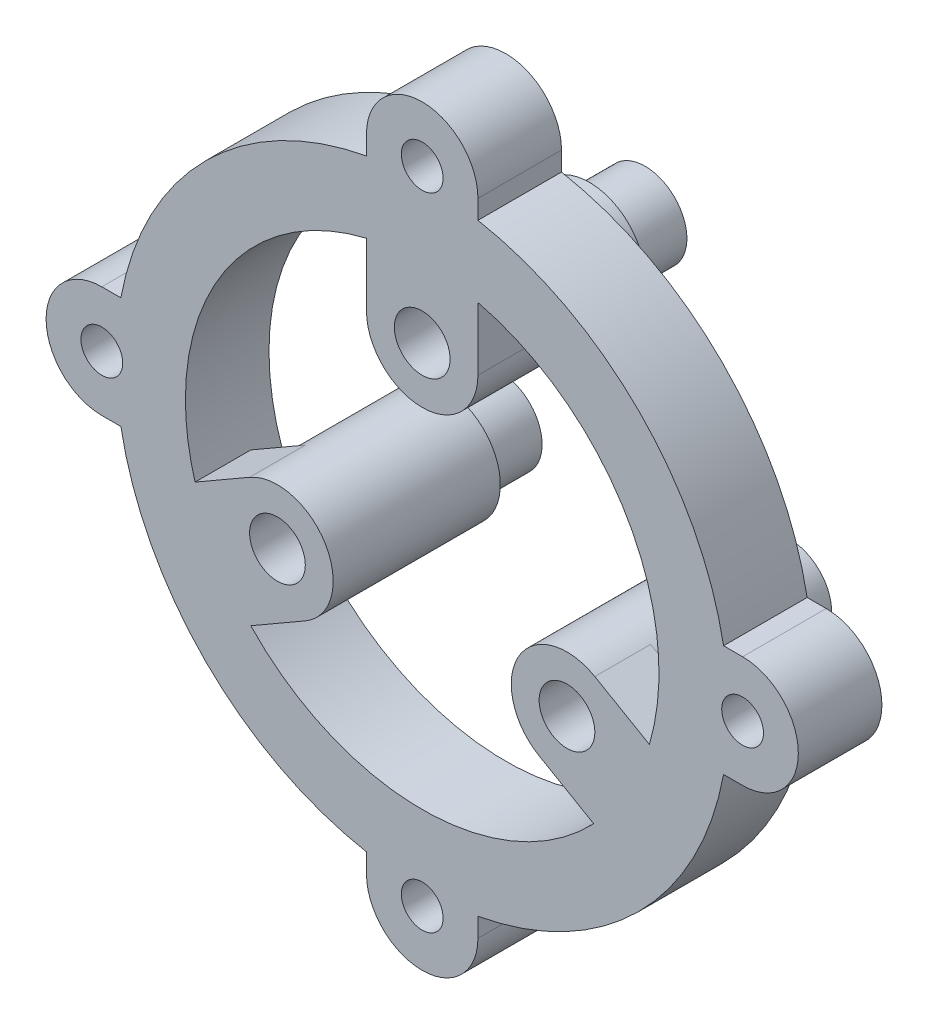
SolidWorks part; units mm, degrees
ref_plane "前视基准面" through (0, 0, 0) normal (0, 0, 1) x (1, 0, 0)
ref_plane "上视基准面" through (0, 0, 0) normal (0, 1, 0) x (1, 0, 0)
ref_plane "右视基准面" through (0, 0, 0) normal (1, 0, 0) x (0, 0, -1)
other "Configuration Table"
sketch "草图1" plane through (0, 0, 0) normal (0, 0, 1) x (1, 0, 0)
  line L0 (9.4853, -3.1669) -> (4, 0)
  line L5 (-2, 9.798) -> (-2, 3.4641)
  line L7 (2, 9.798) -> (2, 3.4641)
  line L8 (7.4853, -6.631) -> (2, -3.4641)
  line L9 (-7.4853, -6.631) -> (-2, -3.4641)
  line L10 (-9.4853, -3.1669) -> (-4, 0)
  circle A1 centre (0, 6) radius 1
  circle A2 centre (5.1962, -3) radius 1
  circle A3 centre (-5.1962, -3) radius 1
  arc A4 (-2, 3.4641) -> (-4, 0) centre (0, 0) ccw
  circle A6 centre (0, 11.5) radius 0.75
  circle A7 centre (11.5, 0) radius 0.75
  circle A8 centre (0, -11.5) radius 0.75
  circle A9 centre (-11.5, 0) radius 0.75
  arc A10 (-2, 9.798) -> (-9.4853, -3.1669) centre (0, 0) ccw
  circle A11 centre (0, 0) radius 13
  arc A13 (-2, -3.4641) -> (2, -3.4641) centre (0, 0) ccw
  arc A14 (-7.4853, -6.631) -> (7.4853, -6.631) centre (0, 0) ccw
  arc A15 (4, 0) -> (2, 3.4641) centre (0, 0) ccw
  arc A16 (9.4853, -3.1669) -> (2, 9.798) centre (0, 0) ccw
  point P12 (0, 0)
  point P22 (0, 0)
  point P35 (0, 0)
  dimension "D1" = 3
  dimension "D2" = 4
  dimension "D3" = 3
extrude "凸台-拉伸1" add sketch "草图1" along normal blind 3
sketch "草图2" plane through (0, 0, 0) normal (0, 0, -1) x (-1, 0, 0)
  circle A0 centre (0, 6) radius 2
  circle A1 centre (0, 6) radius 3
  circle A2 centre (5.1962, -3) radius 3
  circle A3 centre (5.1962, -3) radius 2
  circle A4 centre (-5.1962, -3) radius 3
  circle A5 centre (-5.1962, -3) radius 2
  arc A6 (4, 0) -> (2, 3.4641) centre (0, 0) ccw construction
  circle A7 centre (0, 11.5) radius 0.75
  circle A8 centre (0, 11.5) radius 2
  circle A9 centre (11.5, 0) radius 0.75
  circle A10 centre (11.5, 0) radius 2
  circle A11 centre (0, -11.5) radius 0.75
  circle A12 centre (0, -11.5) radius 2
  circle A13 centre (-11.5, 0) radius 0.75
  circle A14 centre (-11.5, 0) radius 2
  point P13 (0, 0)
  point P30 (0, 0)
  dimension "D1" = 3
  dimension "D2" = 4
extrude "凸台-拉伸2" add sketch "草图2" along normal blind 2 and the other way blind 3
sketch "草图3" plane through (0, 0, 0) normal (0, 0, -1) x (-1, 0, 0)
  line L2 (-2, 11.5) -> (-2, 10.8167)
  line L4 (2, 11.5) -> (2, 10.8167)
  line L5 (11.5, 2) -> (10.8167, 2)
  line L6 (11.5, -2) -> (10.8167, -2)
  line L7 (2, -11.5) -> (2, -10.8167)
  line L8 (-2, -11.5) -> (-2, -10.8167)
  line L9 (-11.5, -2) -> (-10.8167, -2)
  line L10 (-11.5, 2) -> (-10.8167, 2)
  arc A0 (2, 11.5) -> (-2, 11.5) centre (0, 11.5) ccw
  arc A2 (-2, 10.8167) -> (-10.8167, 2) centre (0, 0) ccw
  arc A3 (11.5, -2) -> (11.5, 2) centre (11.5, 0) ccw
  arc A4 (-2, -11.5) -> (2, -11.5) centre (0, -11.5) ccw
  arc A5 (-11.5, 2) -> (-11.5, -2) centre (-11.5, 0) ccw
  arc A6 (-10.8167, -2) -> (-2, -10.8167) centre (0, 0) ccw
  arc A7 (10.8167, 2) -> (2, 10.8167) centre (0, 0) ccw
  arc A8 (2, -10.8167) -> (10.8167, -2) centre (0, 0) ccw
  circle A9 centre (0, 0) radius 2.5
  circle A10 centre (0, 0) radius 24.4878
  point P27 (0, 0)
  arc M18 (9.9239, 1.2312) -> (12.9239, 1.4044) centre (11.5, 0) cw
  arc M19 (12.9239, 1.4044) -> (1.4044, 12.9239) centre (0, 0) ccw
  arc M20 (1.4044, 12.9239) -> (-1.4044, 12.9239) centre (0, 11.5) cw
  arc M21 (-1.4044, 12.9239) -> (-12.9239, 1.4044) centre (0, 0) ccw
  arc M22 (-12.9239, 1.4044) -> (-9.9239, 1.2312) centre (-11.5, 0) cw
  dimension "D1" = 4
extrude "切除-拉伸2" cut sketch "草图3" against normal blind 17 and the other way blind 15 contours A7 L5 L4 M18 M19 M20 | A2 L2 L10 M20 M21 M22 | A10 A8 L7 A4 L8 A6 L9 A5 A0 A3 L6 M21 M19 | A9 region at (7.9654, 7.9654, 0) region at (-7.9654, 7.9654, 0) region at (0, 0, 0) region at (23.7952, 0, 0)
sketch "草图4" plane through (0, 0, 0) normal (0, 0, -1) x (-1, 0, 0)
  circle A0 centre (0, 0) radius 9
  circle A1 centre (0, 0) radius 10
extrude "凸台-拉伸3" add sketch "草图4" against normal blind 3
sketch "草图5" plane through (0, 0, 0) normal (0, 0, -1) x (-1, 0, 0)
  circle A0 centre (0, 6) radius 2.3
  circle A1 centre (5.1962, -3) radius 2.3
  circle A2 centre (-5.1962, -3) radius 2.3
  point P10 (0, 0)
  dimension "D1" = 3
extrude "切除-拉伸3" cut sketch "草图5" along normal blind 6
sketch "草图6" plane through (0, 0, -2) normal (0, 0, -1) x (-1, 0, 0)
  circle A0 centre (0, 6) radius 2.3
  circle A1 centre (0, 6) radius 3.2
  circle A2 centre (5.1962, -3) radius 3.2
  circle A3 centre (5.1962, -3) radius 2.3
  circle A4 centre (-5.1962, -3) radius 3.2
  circle A5 centre (-5.1962, -3) radius 2.3
  point P13 (0, 0)
  dimension "D1" = 3
extrude "凸台-拉伸4" add sketch "草图6" against normal blind 5
sketch "草图7" plane through (0, 0, 0) normal (0, 0, -1) x (-1, 0, 0)
  circle A0 centre (0, 0) radius 8.5
  circle A1 centre (0, 0) radius 9
extrude "凸台-拉伸5" add sketch "草图7" against normal blind 3
sketch "草图8" plane through (0, 0, 0) normal (0, 0, -1) x (-1, 0, 0)
  circle A0 centre (0, 6) radius 2
  circle A1 centre (5.1962, -3) radius 2
  circle A2 centre (-5.1962, -3) radius 2
  point P10 (0, 0)
  dimension "D1" = 3
extrude "切除-拉伸5" cut sketch "草图8" against normal blind 2
chamfer "倒角1" distance 1 angle 45 3 edges at (3.1962, -3, 2) (-7.1962, -3, 2) (-2, 6, 2)
sketch "草图9" plane through (0, 0, 0) normal (0, 0, -1) x (-1, 0, 0)
  circle A0 centre (0, 0) radius 18.0867
extrude "切除-拉伸6" cut sketch "草图9" along normal blind 16
sketch "草图10" plane through (0, 0, 0) normal (0, 0, -1) x (-1, 0, 0)
  line L0 (4.1962, -4.7321) -> (6.1545, -5.8627)
  line L2 (-2, 6) -> (-2, 8.2614)
  line L4 (2, 6) -> (2, 8.2614)
  line L5 (6.1962, -1.2679) -> (8.1545, -2.3986)
  line L6 (-6.1962, -1.2679) -> (-8.1545, -2.3986)
  line L7 (-4.1962, -4.7321) -> (-6.1545, -5.8627)
  arc A0 (-2, 6) -> (2, 6) centre (0, 6) ccw
  circle A1 centre (0, 6) radius 1
  arc A2 (-2, 8.2614) -> (-8.1545, -2.3986) centre (0, 0) ccw
  arc A3 (6.1962, -1.2679) -> (4.1962, -4.7321) centre (5.1962, -3) ccw
  arc A4 (-4.1962, -4.7321) -> (-6.1962, -1.2679) centre (-5.1962, -3) ccw
  arc A5 (8.1545, -2.3986) -> (2, 8.2614) centre (0, 0) ccw
  arc A6 (-6.1545, -5.8627) -> (6.1545, -5.8627) centre (0, 0) ccw
  point P22 (0, 0)
  dimension "D1" = 3
extrude "切除-拉伸7" cut sketch "草图10" against normal blind 10
sketch "草图11" plane through (0, 0, 0) normal (0, 0, -1) x (-1, 0, 0)
  circle A0 centre (0, 6) radius 1
  circle A1 centre (0, 6) radius 2
  circle A2 centre (5.1962, -3) radius 1
  circle A3 centre (5.1962, -3) radius 2
  circle A4 centre (-5.1962, -3) radius 1
  circle A5 centre (-5.1962, -3) radius 2
  point P13 (0, 0)
  dimension "D1" = 3
extrude "凸台-拉伸6" add sketch "草图11" against normal blind 2
sketch "草图12" plane through (0, 0, 0) normal (0, 0, -1) x (-1, 0, 0)
  circle A0 centre (0, 0) radius 8.5
  circle A1 centre (0, 6) radius 2
  circle A2 centre (5.1962, -3) radius 2
  circle A3 centre (-5.1962, -3) radius 2
extrude "切除-拉伸8" cut sketch "草图12" against normal blind 1
sketch "草图13" plane through (0, 0, 0) normal (0, 0, -1) x (-1, 0, 0)
  circle A0 centre (0, 6) radius 1
  circle A1 centre (0, 6) radius 2
  circle A2 centre (5.1962, -3) radius 1
  circle A3 centre (5.1962, -3) radius 2
  circle A4 centre (-5.1962, -3) radius 1
  circle A5 centre (-5.1962, -3) radius 2
  point P13 (0, 0)
  dimension "D1" = 3
extrude "凸台-拉伸7" add sketch "草图13" along normal blind 5
sketch "草图14" plane through (0, 0, -5) normal (0, 0, -1) x (-1, 0, 0)
  circle A0 centre (0, 6) radius 1.5
  circle A1 centre (5.1962, -3) radius 1.5
  circle A2 centre (-5.1962, -3) radius 1.5
  circle A3 centre (0, 0) radius 12.8394
  point P10 (0, 0)
  dimension "D1" = 3
extrude "切除-拉伸10" cut sketch "草图14" against normal blind 2
